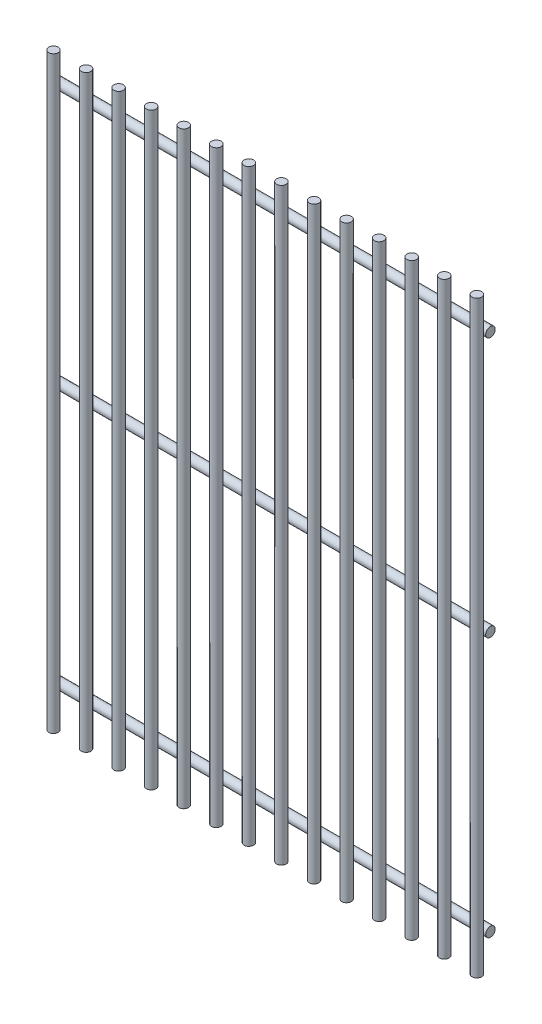
SolidWorks part; units mm, degrees
material "201 Annealed Stainless Steel (SS)"
ref_plane "Front Plane" through (0, 0, 0) normal (0, 0, 1) x (1, 0, 0)
ref_plane "Top Plane" through (0, 0, 0) normal (0, 1, 0) x (1, 0, 0)
ref_plane "Right Plane" through (0, 0, 0) normal (1, 0, 0) x (0, 0, -1)
sketch "Sketch1" plane through (0, 0, 0) normal (0, 1, 0) x (1, 0, 0)
  line L0 (-158.75, 0) -> (158.75, 0) construction
  line L1 (-158.75, 0) -> (-158.75, -10.4586) construction
  circle A0 centre (-155.25, -3.5) radius 3.5
  dimension "D2" = 7
  dimension "D1" = 317.5
extrude "Boss-Extrude1" add sketch "Sketch1" along normal mid plane 431.8
pattern_linear "LPattern1" count 14 spacing 23.8846 along (1, 0, 0) of bodies 101
sketch "Sketch2" plane through (0, 0, 0) normal (1, 0, 0) x (0, 0, -1)
  line L0 (0, 215.9) -> (-7, 215.9) construction
  line L1 (-7, -215.9) -> (0, -215.9) construction
  circle A0 centre (3, -190.5) radius 3.5
  circle A1 centre (3, 190.5) radius 3.5
  circle A2 centre (3, 0) radius 3.5
  point P6 (23.1189, -105.2279)
  point P7 (0, 0)
  point P9 (0, 0)
  dimension "D1" = 7
  dimension "D2" = 3
  dimension "D3" = 25.4
  dimension "D4" = 25.4
extrude "Boss-Extrude2" add sketch "Sketch2" along normal mid plane 317.5
equation "\"D3@LPattern1\"=(\"D1@Sketch1\"-(7mm))/13"
equation "\"D4@Sketch2\"=\"D3@Sketch2\""
